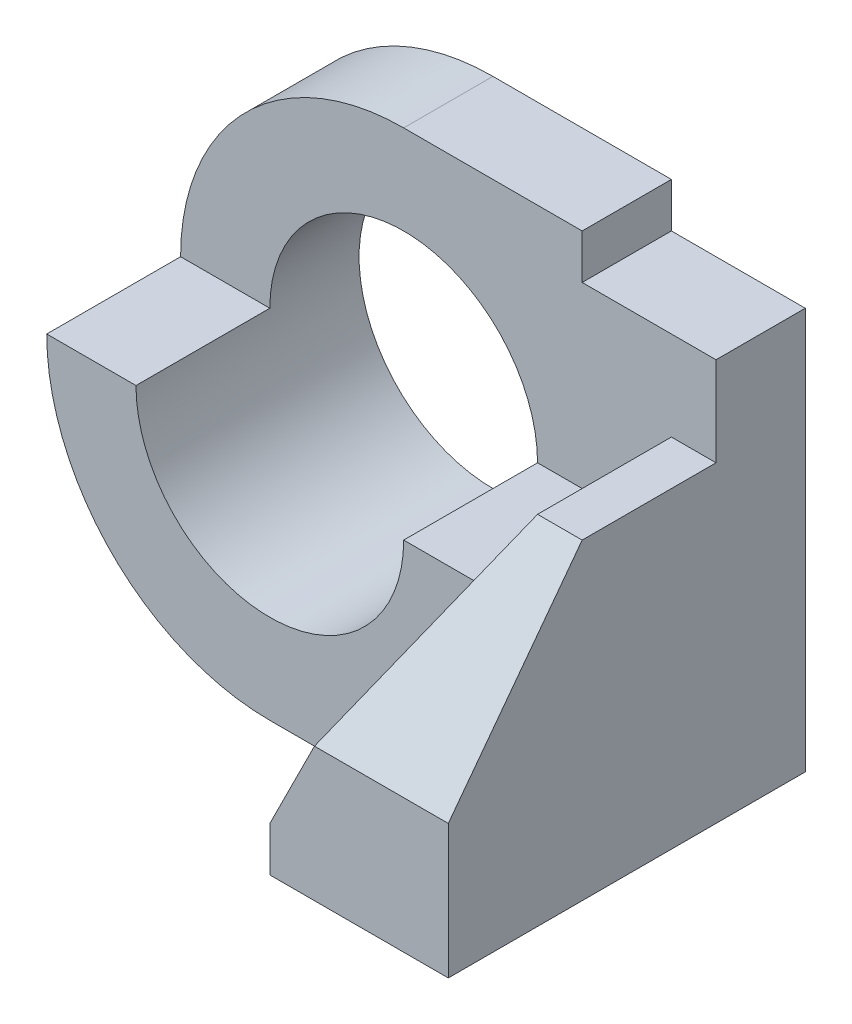
SolidWorks part; units mm, degrees
ref_plane "Front" through (0, 0, 0) normal (0, 0, 1) x (1, 0, 0)
ref_plane "Top" through (0, 0, 0) normal (0, 1, 0) x (1, 0, 0)
ref_plane "Right" through (0, 0, 0) normal (1, 0, 0) x (0, 0, -1)
sketch "Sketch1" plane through (0, 0, 0) normal (0, 0, 1) x (1, 0, 0)
  line L0 (0, 0) -> (7, 0)
  line L1 (7, 0) -> (7, 9)
  line L2 (7, 9) -> (4, 9)
  line L3 (4, 9) -> (4, 10)
  line L4 (4, 10) -> (0, 10)
  arc A0 (0, 10) -> (0, 0) centre (0, 5) ccw
  circle A1 centre (0, 5) radius 3
  dimension "D4" = 5
  dimension "D5" = 6
  dimension "D1" = 7
  dimension "D2" = 9
  dimension "D3" = 4
extrude "Boss-Extrude1" add sketch "Sketch1" along normal blind 5
sketch "Sketch2" plane through (0, 0, 5) normal (0, 0, 1) x (1, 0, 0)
  line L1 (-5, 5) -> (9.2777, 5)
  line L2 (-5, 5) -> (-5, 10.6103)
  line L3 (-5, 10.6103) -> (9.2777, 10.6103)
  line L4 (9.2777, 5) -> (9.2777, 10.6103)
  arc A0 (0, 10) -> (0, 0) centre (0, 5) ccw construction
extrude "Cut-Extrude1" cut sketch "Sketch2" against normal blind 3
sketch "Sketch3" plane through (0, 0, 2) normal (0, 0, 1) x (1, 0, 0)
  line L0 (7, 7) -> (6, 7)
  line L1 (7, 9) -> (7, 5) construction
  line L2 (6, 7) -> (3, 1)
  line L3 (3, 1) -> (3, 0)
  line L4 (0, 0) -> (7, 0) construction
  line L5 (3, 0) -> (7, 0)
  line L6 (7, 0) -> (7, 7)
  dimension "D1" = 1
  dimension "D2" = 7
  dimension "D3" = 1
  dimension "D4" = 4
extrude "Boss-Extrude2" add sketch "Sketch3" along normal blind 6
fillet "Chamfer1" radius 3 1 edges at (6.5, 7, 8) profile chamfer first distance on face at (6.5, 7, 5)
